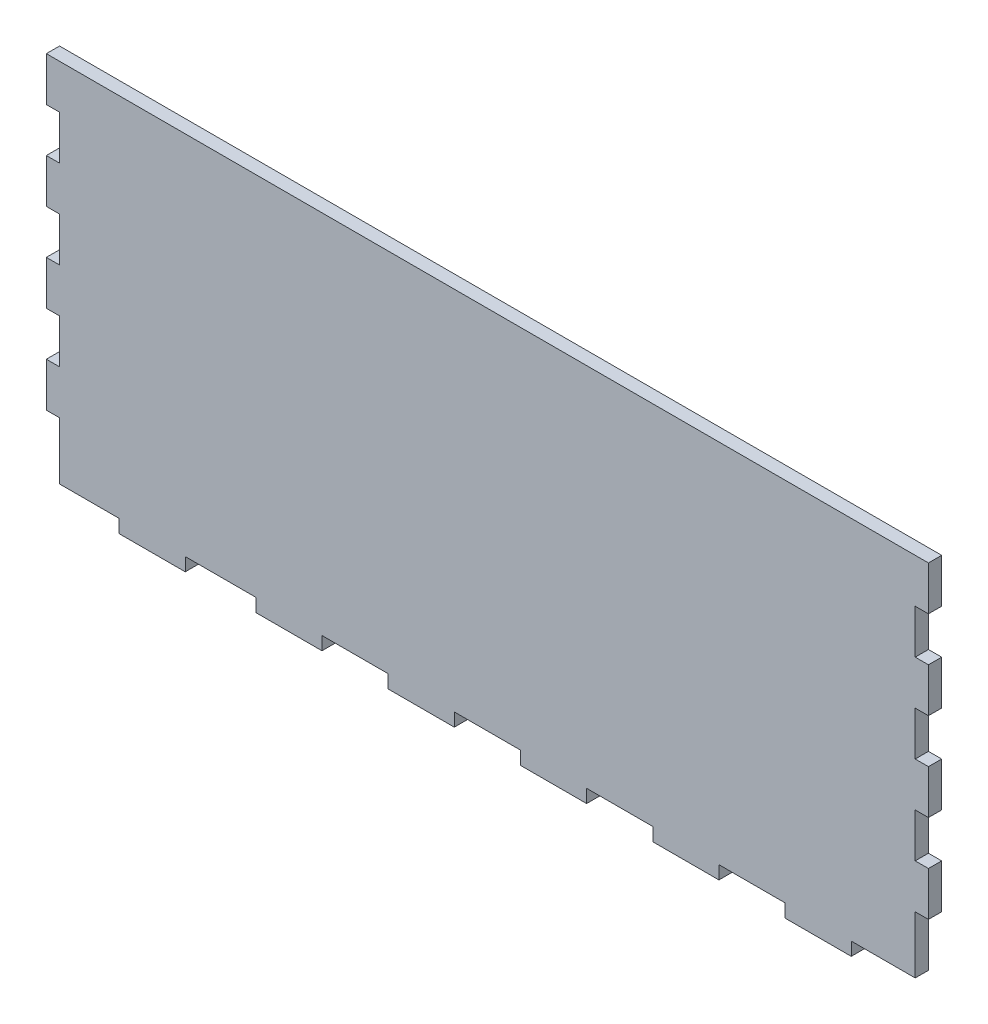
SolidWorks part; units mm, degrees
ref_plane "Front Plane" through (0, 0, 0) normal (0, 0, 1) x (1, 0, 0)
ref_plane "Top Plane" through (0, 0, 0) normal (0, 1, 0) x (1, 0, 0)
ref_plane "Right Plane" through (0, 0, 0) normal (1, 0, 0) x (0, 0, -1)
sketch "Sketch1" plane through (0, 0, 0) normal (0, 0, 1) x (1, 0, 0)
  line L0 (-97, 0) -> (97, 0) construction
  line L1 (0, -25.5) -> (0, 57.5) construction
  line L2 (-97, -12.5) -> (-97, -25.5)
  line L3 (-97, 57.5) -> (97, 57.5)
  line L4 (-100, -12.5) -> (-97, -12.5)
  line L5 (0, -25.5) -> (7.5, -25.5)
  line L6 (-100, -2.5) -> (-100, -12.5)
  line L7 (-97, -2.5) -> (-100, -2.5)
  line L8 (-97, 57.5) -> (-100, 57.5)
  line L9 (-100, 57.5) -> (-100, 47.5)
  line L10 (-100, 47.5) -> (-97, 47.5)
  line L11 (-97, 47.5) -> (-97, 37.5)
  line L12 (-97, 37.5) -> (-100, 37.5)
  line L13 (-100, 37.5) -> (-100, 27.5)
  line L14 (100, 17.5) -> (100, 7.5)
  line L15 (-100, 27.5) -> (-97, 27.5)
  line L16 (-97, 27.5) -> (-97, 17.5)
  line L17 (97, 7.5) -> (100, 7.5)
  line L18 (97, 17.5) -> (100, 17.5)
  line L19 (97, 7.5) -> (97, -2.5)
  line L20 (97, 27.5) -> (97, 17.5)
  line L21 (100, 27.5) -> (97, 27.5)
  line L22 (100, 37.5) -> (100, 27.5)
  line L23 (97, 37.5) -> (100, 37.5)
  line L24 (97, 47.5) -> (97, 37.5)
  line L25 (100, 47.5) -> (97, 47.5)
  line L26 (100, 57.5) -> (100, 47.5)
  line L27 (97, 57.5) -> (100, 57.5)
  line L28 (7.5, -25.5) -> (7.5, -28.5)
  line L29 (7.5, -28.5) -> (22.5, -28.5)
  line L30 (22.5, -28.5) -> (22.5, -25.5)
  line L31 (30, -25.5) -> (37.5, -25.5)
  line L32 (37.5, -25.5) -> (37.5, -28.5)
  line L33 (37.5, -28.5) -> (52.5, -28.5)
  line L34 (52.5, -28.5) -> (52.5, -25.5)
  line L35 (60, -25.5) -> (67.5, -25.5)
  line L36 (67.5, -25.5) -> (67.5, -28.5)
  line L37 (67.5, -28.5) -> (82.5, -28.5)
  line L38 (82.5, -28.5) -> (82.5, -25.5)
  line L39 (22.5, -25.5) -> (30, -25.5)
  line L40 (52.5, -25.5) -> (60, -25.5)
  line L41 (82.5, -25.5) -> (97, -25.5)
  line L42 (0, -25.5) -> (-7.5, -25.5)
  line L43 (-7.5, -25.5) -> (-7.5, -28.5)
  line L44 (-7.5, -28.5) -> (-22.5, -28.5)
  line L45 (-22.5, -28.5) -> (-22.5, -25.5)
  line L46 (-22.5, -25.5) -> (-37.5, -25.5)
  line L47 (-37.5, -25.5) -> (-37.5, -28.5)
  line L48 (-37.5, -28.5) -> (-52.5, -28.5)
  line L49 (-52.5, -28.5) -> (-52.5, -25.5)
  line L50 (-52.5, -25.5) -> (-68.5, -25.5)
  line L51 (-68.5, -25.5) -> (-68.5, -28.5)
  line L52 (97, -2.5) -> (100, -2.5)
  line L53 (100, -2.5) -> (100, -12.5)
  line L54 (100, -12.5) -> (97, -12.5)
  line L55 (97, -12.5) -> (97, -25.5)
  line L56 (-97, 7.5) -> (-97, -2.5)
  line L57 (-97, 17.5) -> (-100, 17.5)
  line L58 (-97, 7.5) -> (-100, 7.5)
  line L59 (-100, 17.5) -> (-100, 7.5)
  line L60 (-68.5, -28.5) -> (-83.5, -28.5)
  line L62 (-83.5, -28.5) -> (-83.5, -25.5)
  line L63 (-83.5, -25.5) -> (-97, -25.5)
  dimension "D2" = 7.5
  dimension "D4" = 83
  dimension "D5" = 10
  dimension "D6" = 194
  dimension "D8" = 7.5
  dimension "D9" = 15
  dimension "D10" = 3
  dimension "D11" = 10
  dimension "D7" = 10
  dimension "D13" = 10
  dimension "D12" = 10
  dimension "D14" = 7.5
  dimension "D15" = 14.5
  dimension "D16" = 10
  dimension "D17" = 10
  dimension "D18" = 3
  dimension "D19" = 15
  dimension "D20" = 15
  dimension "D21" = 15
  dimension "D22" = 16
  dimension "D23" = 15
extrude "Boss-Extrude1" add sketch "Sketch1" along normal blind 3
